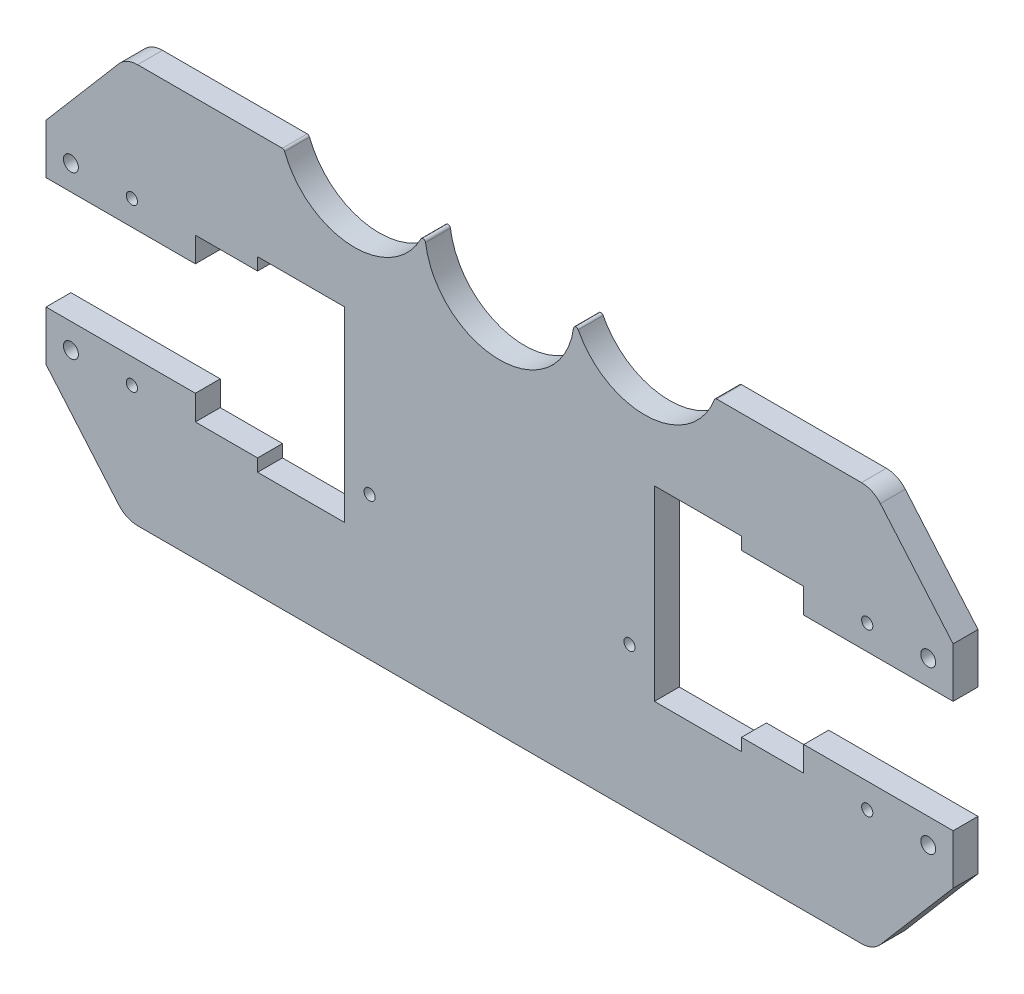
SolidWorks part; units mm, degrees
ref_plane "Plan de face" through (0, 0, 0) normal (0, 0, 1) x (1, 0, 0)
ref_plane "Plan de dessus" through (0, 0, 0) normal (0, 1, 0) x (1, 0, 0)
ref_plane "Plan de droite" through (0, 0, 0) normal (1, 0, 0) x (0, 0, -1)
sketch "Esquisse3" plane through (0, 0, 0) normal (0, 0, 1) x (1, 0, 0)
  line L0 (-182.2, 42.5) -> (-150, 80.2)
  line L1 (-182.2, 42.5) -> (182.2, 42.5)
  line L2 (-182.2, 42.5) -> (-182.2, -42.5)
  line L3 (-182.2, -42.5) -> (182.2, -42.5)
  line L4 (182.2, 42.5) -> (182.2, -42.5)
  line L5 (-150, 80.2) -> (150, 80.2)
  line L6 (-150, 80.2) -> (-150, 42.5)
  line L7 (-150, 42.5) -> (150, 42.5)
  line L8 (150, 80.2) -> (150, 42.5)
  line L9 (-150, -80.2) -> (150, -80.2)
  line L10 (-150, -80.2) -> (-150, -42.5)
  line L11 (-150, -42.5) -> (150, -42.5)
  line L12 (150, -80.2) -> (150, -42.5)
  line L13 (150, 80.2) -> (182.2, 42.5)
  line L14 (182.2, -42.5) -> (150, -80.2)
  line L15 (-150, -80.2) -> (-182.2, -42.5)
  dimension "D1" = 85
  dimension "D2" = 300
  dimension "D3" = 300
  dimension "D4" = 32.2
  dimension "D5" = 0
  dimension "D6" = 32.2
  dimension "D7" = 37.7
  dimension "D8" = 37.7
  dimension "D9" = 150
  dimension "D10" = 42.5
extrude "Boss.-Extru.1" add sketch "Esquisse3" along normal blind 10 contours L4 L1 L2 L3 | L8 L5 L6 L1 | L9 L12 L3 L10 | L6 L0 L1 | L15 L10 L3 | L14 L3 L12 | L13 L8 L1 region at (-160.7333, 55.0667, 0) region at (0, 0, 0) region at (0, 61.35, 0) region at (-160.7333, -55.0667, 0) region at (160.7333, 55.0667, 0) region at (0, -61.35, 0) region at (160.7333, -55.0667, 0)
sketch "Esquisse4" plane through (0, 0, 10) normal (0, 0, 1) x (1, 0, 0)
  line L1 (-182.2, 32.5) -> (-97.2, 32.5)
  line L2 (-182.2, 32.5) -> (-182.2, -32.5)
  line L3 (-182.2, -32.5) -> (-97.2, -32.5)
  line L4 (-97.2, 32.5) -> (-97.2, -32.5)
  line L5 (-97.2, -37.5) -> (-62.2, -37.5)
  line L6 (-97.2, -37.5) -> (-97.2, 37.5)
  line L7 (-97.2, 37.5) -> (-62.2, 37.5)
  line L8 (-62.2, -37.5) -> (-62.2, 37.5)
  line L9 (182.2, 32.5) -> (97.2, 32.5)
  line L10 (182.2, 32.5) -> (182.2, -32.5)
  line L11 (182.2, -32.5) -> (97.2, -32.5)
  line L12 (97.2, 32.5) -> (97.2, -32.5)
  line L13 (97.2, 37.5) -> (62.2, 37.5)
  line L14 (97.2, 37.5) -> (97.2, -37.5)
  line L15 (97.2, -37.5) -> (62.2, -37.5)
  line L16 (62.2, 37.5) -> (62.2, -37.5)
  line L17 (-182.2, 32.5) -> (-122.2, 32.5)
  line L18 (-182.2, 32.5) -> (-182.2, 22.5)
  line L19 (-182.2, 22.5) -> (-122.2, 22.5)
  line L20 (-122.2, 32.5) -> (-122.2, 22.5)
  line L21 (-182.2, -32.5) -> (-122.2, -32.5)
  line L22 (-182.2, -32.5) -> (-182.2, -22.5)
  line L23 (-182.2, -22.5) -> (-122.2, -22.5)
  line L24 (-122.2, -32.5) -> (-122.2, -22.5)
  line L25 (182.2, 32.5) -> (122.2, 32.5)
  line L26 (182.2, 32.5) -> (182.2, 22.5)
  line L27 (182.2, 22.5) -> (122.2, 22.5)
  line L28 (122.2, 32.5) -> (122.2, 22.5)
  line L29 (182.2, -32.5) -> (122.2, -32.5)
  line L30 (182.2, -32.5) -> (182.2, -22.5)
  line L31 (182.2, -22.5) -> (122.2, -22.5)
  line L32 (122.2, -32.5) -> (122.2, -22.5)
  line L34 (-182.2, 42.5) -> (-182.2, -42.5) construction
  line M16 (182.2, -42.5) -> (182.2, 42.5)
  line M20 (-182.2, 42.5) -> (-182.2, -42.5)
  dimension "D1" = 85
  dimension "D2" = 5
  dimension "D3" = 5
  dimension "D4" = 35
  dimension "D5" = 85
  dimension "D6" = 85
  dimension "D7" = 35
  dimension "D8" = 85
  dimension "D9" = 5
  dimension "D10" = 5
  dimension "D11" = 0
  dimension "D12" = 60
  dimension "D13" = 10
  dimension "D14" = 10
  dimension "D15" = 0
  dimension "D16" = 10
  dimension "D17" = 10
  dimension "D18" = 60
  dimension "D19" = 10
  dimension "D20" = 10
  dimension "D21" = 0
  dimension "D22" = 10
  dimension "D23" = 10
extrude "Enlèv. mat.-Extru.1" cut sketch "Esquisse4" against normal blind 10 contours L4 L1 L3 M20 | L5 L8 L7 L6 L4 | L13 L16 L15 L14 L12 | L9 L12 L11 M16 region at (-136.2318, 0, 10) region at (-79.7, 0, 10) region at (136.2318, 0, 10) region at (79.7, 0, 10)
sketch "Esquisse5" plane through (0, 0, 10) normal (0, 0, 1) x (1, 0, 0)
  line L1 (-150, 80.2) -> (150, 80.2) construction
  arc A0 (30, 80.2) -> (-30, 80.2) centre (0, 80.2) cw
  arc A1 (-30, 80.2) -> (-86.5685, 80.2) centre (-58.2843, 90.2) cw
  arc A2 (30, 80.2) -> (86.5685, 80.2) centre (58.2843, 90.2) ccw
  point P6 (0, 80.2)
  dimension "D1" = 0
  dimension "D2" = 30
  dimension "D3" = 30
  dimension "D6" = 30
  dimension "D4" = 10
  dimension "D5" = 10
extrude "Enlèv. mat.-Extru.2" cut sketch "Esquisse5" against normal blind 10 and the other way through all
sketch "Esquisse11" plane through (0, 0, 10) normal (0, 0, 1) x (1, 0, 0)
  line L0 (182.2, 42.5) -> (182.2, 22.5) construction
  line L1 (-182.2, 42.5) -> (-162.2, 42.5)
  line L2 (-182.2, 42.5) -> (-182.2, 22.5)
  line L3 (-182.2, 22.5) -> (-162.2, 22.5)
  line L4 (-162.2, 42.5) -> (-162.2, 22.5)
  line L6 (182.2, -22.5) -> (182.2, -42.5) construction
  line L7 (-182.2, -22.5) -> (-162.2, -22.5)
  line L8 (-182.2, -22.5) -> (-182.2, -42.5)
  line L9 (-182.2, -42.5) -> (-162.2, -42.5)
  line L10 (-162.2, -22.5) -> (-162.2, -42.5)
  line L11 (182.2, 22.5) -> (122.2, 22.5) construction
  line L12 (162.2, 42.5) -> (182.2, 42.5)
  line L13 (162.2, 42.5) -> (162.2, 22.5)
  line L14 (162.2, 22.5) -> (182.2, 22.5)
  line L15 (182.2, 42.5) -> (182.2, 22.5)
  line L16 (162.2, -22.5) -> (182.2, -22.5)
  line L17 (162.2, -22.5) -> (162.2, -42.5)
  line L18 (162.2, -42.5) -> (182.2, -42.5)
  line L19 (182.2, -22.5) -> (182.2, -42.5)
  line L20 (-182.2, -22.5) -> (-182.2, -42.5) construction
  line L22 (-182.2, 42.5) -> (-182.2, 22.5) construction
  line L23 (182.2, -22.5) -> (122.2, -22.5) construction
  line L24 (-182.2, -22.5) -> (-122.2, -22.5) construction
  line L25 (-182.2, 22.5) -> (-122.2, 22.5) construction
  point P24 (172.2, 22.5)
  dimension "D1" = 20
  dimension "D2" = 20
  dimension "D3" = 0
  dimension "D4" = 0
  dimension "D5" = 20
  dimension "D6" = 20
  dimension "D7" = 0
  dimension "D8" = 0
  dimension "D9" = 20
  dimension "D10" = 20
  dimension "D11" = 20
  dimension "D12" = 20
  dimension "D13" = 0
  dimension "D14" = 0
  dimension "D15" = 0
  dimension "D16" = 0
sketch "Esquisse10" plane through (0, 0, 10) normal (0, 0, 1) x (1, 0, 0)
  line L1 (-182.2, 42.5) -> (-162.2, 42.5) construction
  line L2 (162.2, -22.5) -> (162.2, -42.5) construction
  line L3 (-182.2, 22.5) -> (-162.2, 22.5) construction
  line L4 (-162.2, 42.5) -> (-162.2, 22.5) construction
  line L5 (-182.2, -22.5) -> (-182.2, -42.5) construction
  line L6 (-182.2, -22.5) -> (-162.2, -22.5) construction
  line L8 (162.2, 42.5) -> (182.2, 42.5) construction
  line L10 (162.2, 42.5) -> (162.2, 22.5) construction
  line L11 (182.2, -22.5) -> (182.2, -42.5) construction
  line L12 (162.2, -22.5) -> (182.2, -22.5) construction
  line L13 (162.2, -42.5) -> (182.2, -42.5) construction
  line L15 (-162.2, -22.5) -> (-162.2, -42.5) construction
  circle A1 centre (-147.7, 32.5) radius 2.25
  circle A2 centre (-172.2, 32.5) radius 3
  circle A3 centre (-172.2, -32.5) radius 3
  circle A4 centre (-147.7, -32.5) radius 2.25
  circle A6 centre (172.2, 32.5) radius 3
  circle A8 centre (147.7, 32.5) radius 2.25
  circle A9 centre (172.2, -32.5) radius 3
  circle A10 centre (147.7, -32.5) radius 2.25
  dimension "D4" = 4.5
  dimension "D9" = 6
  dimension "D10" = 6
  dimension "D17" = 6
  dimension "D18" = 4.5
  dimension "D24" = 4.5
  dimension "D28" = 6
  dimension "D35" = 4.5
  dimension "D15" = 14.5
  dimension "D16" = 14.5
  dimension "D5" = 14.5
  dimension "D13" = 14.5
  dimension "D6" = 10
  dimension "D7" = 10
  dimension "D8" = 10
  dimension "D11" = 10
  dimension "D12" = 10
  dimension "D14" = 10
  dimension "D22" = 10
  dimension "D23" = 10
  dimension "D27" = 10
  dimension "D29" = 10
  dimension "D30" = 10
  dimension "D34" = 10
extrude "Enlèv. mat.-Extru.3" cut sketch "Esquisse10" against normal blind 10
sketch "Esquisse13" plane through (0, 0, 10) normal (0, 0, 1) x (1, 0, 0)
  line L0 (-62.2, -37.5) -> (-62.2, 37.5) construction
  line L1 (-62, 1.8) -> (62, 1.8)
  line L2 (-62, 1.8) -> (-62, -8.2)
  line L3 (-62, -8.2) -> (62, -8.2)
  line L4 (62, 1.8) -> (62, -8.2)
  line L5 (62.2, 37.5) -> (62.2, -37.5) construction
  line L7 (-150, -80.2) -> (150, -80.2) construction
  dimension "D1" = 0.2
  dimension "D2" = 0.2
  dimension "D3" = 10
  dimension "D4" = 72
sketch "Esquisse15" plane through (0, 0, 10) normal (0, 0, 1) x (1, 0, 0)
  line L1 (-62.2, -37.5) -> (-62.2, 37.5) construction
  line L2 (62.2, 37.5) -> (62.2, -37.5) construction
  line L4 (-62, -8.2) -> (62, -8.2) construction
  circle A0 centre (-52.2, -22.7) radius 2.25
  circle A1 centre (52.2, -22.7) radius 2.25
  dimension "D1" = 4.5
  dimension "D2" = 4.5
  dimension "D4" = 14.5
  dimension "D3" = 14.5
  dimension "D5" = 10
  dimension "D6" = 10
extrude "Enlèv. mat.-Extru.4" cut sketch "Esquisse15" against normal blind 10
fillet "Congé1" radius 10 4 edges at (150, 80.2, 5) (150, -80.2, 5) (-150, 80.2, 5) (-150, -80.2, 5)
fillet "Congé3" radius 1 4 edges at (-86.5685, 80.2, 5) (-30, 80.2, 5) (30, 80.2, 5) (86.5685, 80.2, 5)
